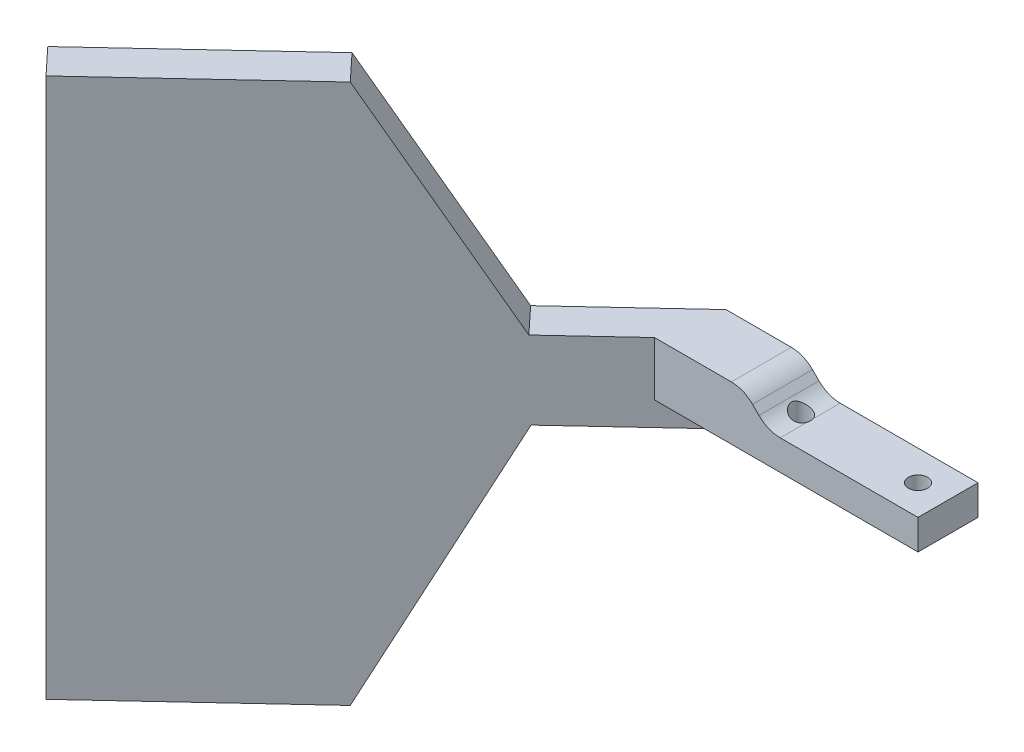
SolidWorks part; units mm, degrees
ref_plane "Front" through (0, 0, 0) normal (0, 0, 1) x (1, 0, 0)
ref_plane "Top" through (0, 0, 0) normal (0, 1, 0) x (1, 0, 0)
ref_plane "Right" through (0, 0, 0) normal (1, 0, 0) x (0, 0, -1)
sketch "Sketch1" plane through (0, 0, 0) normal (0, 1, 0) x (1, 0, 0)
  line L0 (0, 10) -> (0, 0)
  line L1 (0, 0) -> (42, 0)
  line L3 (0, 10) -> (42, 10)
  line L4 (42, 0) -> (42, 10)
  line L9 (0, 10) -> (-58.5083, -44.5599)
  line L10 (-58.5083, -44.5599) -> (-54.4163, -48.948)
  line L11 (0, 10) -> (4.092, 5.6119)
  line L12 (-54.4163, -48.948) -> (4.092, 5.6119)
  line L13 (0, 0) -> (-1.926, 0)
  line L14 (-1.926, 0) -> (0, 1.796)
  line L15 (0, 1.796) -> (0, 0)
  dimension "D1" = 10
  dimension "D2" = 42
  dimension "D3" = 223
  dimension "D4" = 80
  dimension "D5" = 6
  dimension "D6" = 270
extrude "Boss-Extrude1" add sketch "Sketch1" along normal blind 5 contours L10 L12 L1 L0 L9 | L1 L12 L11 L0 | L12 L1 L4 L3 L11 | L13 L0 L12 region at (1.364, 0, -5.8026) region at (-28.2435, 0, 20.3899) region at (21.8174, 0, -4.9666) region at (-0.642, 0, -0.5987)
sketch "Sketch2" plane through (0, 5, 0) normal (0, 1, 0) x (1, 0, 0)
  circle A0 centre (37, 5) radius 1.3
extrude "Cut-Extrude1" cut sketch "Sketch2" against normal blind 10
sketch "Sketch3" plane through (0, 5, 0) normal (0, 1, 0) x (1, 0, 0)
  line L0 (-58.5083, -44.5599) -> (-54.4163, -48.948)
  line L1 (-54.4163, -48.948) -> (-28.1712, -24.474)
  line L2 (-54.4163, -48.948) -> (-1.926, 0) construction
  line L3 (-28.1712, -24.474) -> (-32.2631, -20.0859)
  line L4 (0, 10) -> (-58.5083, -44.5599) construction
  line L5 (-32.2631, -20.0859) -> (-58.5083, -44.5599)
extrude "Boss-Extrude2" add sketch "Sketch3" along normal blind 40
sketch "Sketch4" plane through (0, 0, 0) normal (0, -1, 0) x (1, 0, 0)
  line L0 (-58.5083, 44.5599) -> (-54.4163, 48.948)
  line L1 (-54.4163, 48.948) -> (-28.1712, 24.474)
  line L2 (-54.4163, 48.948) -> (-1.926, 0) construction
  line L3 (-28.1712, 24.474) -> (-32.2631, 20.0859)
  line L4 (0, -10) -> (-58.5083, 44.5599) construction
  line L5 (-32.2631, 20.0859) -> (-58.5083, 44.5599)
extrude "Boss-Extrude3" add sketch "Sketch4" along normal blind 45
sketch "Sketch5" plane through (-4.9878, 0, -5.3488) normal (-0.682, 0, -0.7314) x (-0.7314, 0, 0.682)
  line L0 (37.2943, -45) -> (37.2943, 0)
  line L1 (37.2943, 0) -> (13.889, 0)
  line L2 (-6.82, 0) -> (37.2943, 0) construction
  line L3 (13.889, 0) -> (37.2943, -45)
  line L4 (13.889, 5) -> (37.2943, 45)
  line L5 (-6.82, 5) -> (37.2943, 5) construction
  line L6 (37.2943, 45) -> (37.2943, 5)
  line L7 (37.2943, 5) -> (13.889, 5)
extrude "Boss-Extrude4" add sketch "Sketch5" against normal blind 6
sketch "Sketch6" plane through (0, 0, 0) normal (0, -1, 0) x (1, 0, 0)
  circle A0 centre (37, -5) radius 4.9
  circle A1 centre (37, -5) radius 1.3
extrude "Boss-Extrude5" [suppressed] add sketch "Sketch6" along normal blind 0.9
sketch "Sketch8" plane through (0, 0, 0) normal (0, -1, 0) x (1, 0, 0)
  line L0 (0, -10) -> (-23.7044, 12.1047)
  line L1 (-32.2631, 20.0859) -> (-15.1456, 4.1235) construction
  line L6 (-23.7044, 12.1047) -> (-19.6124, 16.4928)
  line L7 (-28.1712, 24.474) -> (-11.0536, 8.5116) construction
  line L8 (-19.6124, 16.4928) -> (8.7977, -10)
  line L9 (0, -10) -> (42, -10) construction
  line L10 (8.7977, -10) -> (0, -10)
extrude "Boss-Extrude6" add sketch "Sketch8" along normal blind 4
sketch "Sketch9" plane through (0, 5, 0) normal (0, 1, 0) x (1, 0, 0)
  line L3 (-16.6671, -5.5424) -> (-32.2631, -20.0859) construction
  line L4 (-24.4651, -12.8141) -> (0, 10)
  line L6 (-24.4651, -12.8141) -> (-16.7996, -13.8699)
  line L7 (-28.1712, -24.474) -> (-11.0536, -8.5116) construction
  line L9 (-16.7996, -13.8699) -> (8.7977, 10)
  line L10 (0, 10) -> (42, 10) construction
  line L11 (8.7977, 10) -> (0, 10)
  line L12 (42, 0) -> (-1.926, 0) construction
  line L13 (8.7977, 0) -> (-1.926, 0)
  line L14 (-1.926, 0) -> (8.7977, 10)
  line L15 (8.7977, 10) -> (17.9505, 10)
  line L16 (17.9505, 10) -> (17.9505, 0)
  line L17 (17.9505, 0) -> (8.7977, 0)
  line M1 (-15.1456, -4.1235) -> (-11.0536, -8.5116)
  line M2 (-11.0536, -8.5116) -> (-1.926, 0)
  line M3 (-1.926, 0) -> (42, 0)
  line M6 (42, 10) -> (0, 10)
  line M7 (0, 10) -> (-15.1456, -4.1235)
extrude "Boss-Extrude7" add sketch "Sketch9" along normal blind 4 contours L9 M3 | L9 M2 M6 M7 M1 | L6 L9 L4 M1 region at (-17.0984, 5, 9.7222) region at (-4.2059, 5, -1.7921) region at (10.3631, 5, -4.3843)
fillet "Fillet2" [suppressed] radius 15
fillet "Fillet7" radius 5 1 edges at (17.9505, 9, -5) profile chamfer
fillet "Fillet8" radius 5 2 edges at (12.9505, 9, -5) (16.9505, 5, -5)
sketch "Sketch11" plane through (0, 0, 0) normal (0, -1, 0) x (-1, 0, 0)
  circle A0 centre (-17.5, 5) radius 1.6
extrude "Cut-Extrude2" cut sketch "Sketch11" against normal blind 10
sketch "Sketch12" plane through (0, 0, 0) normal (0, -1, 0) x (-1, 0, 0)
  circle A0 centre (-37, 5) radius 1.6
extrude "Cut-Extrude5" cut sketch "Sketch12" against normal through all both and the other way through all
